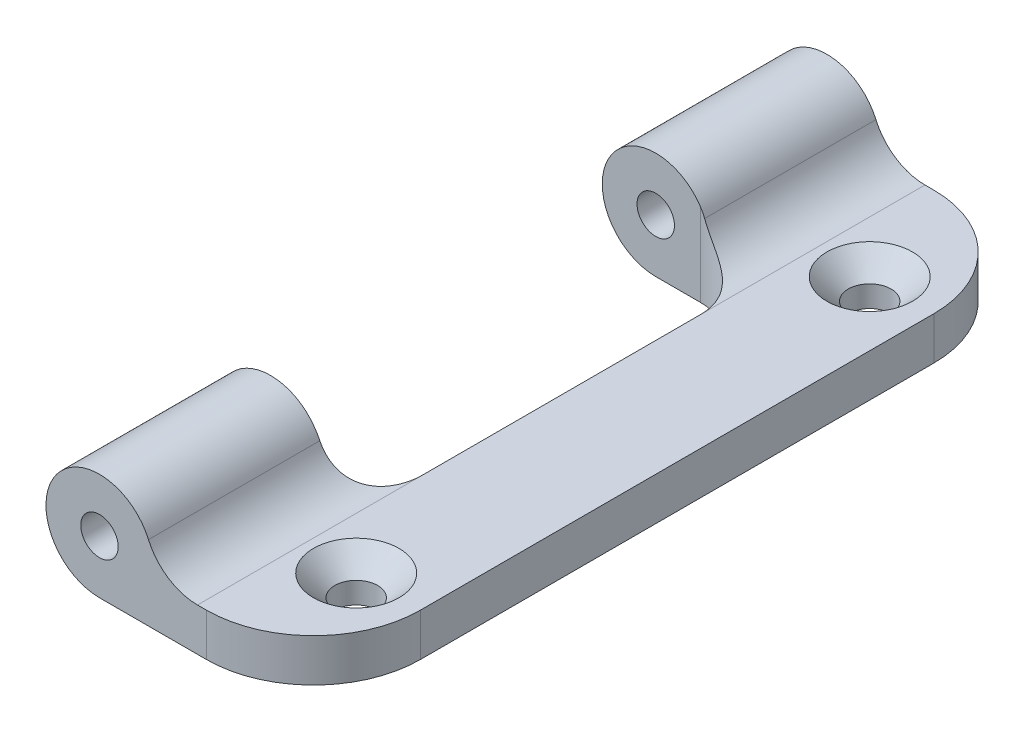
SolidWorks part; units mm, degrees
ref_plane "Plan de face" through (0, 0, 0) normal (0, 0, 1) x (1, 0, 0)
ref_plane "Plan de dessus" through (0, 0, 0) normal (0, 1, 0) x (1, 0, 0)
ref_plane "Plan de droite" through (0, 0, 0) normal (1, 0, 0) x (0, 0, -1)
sketch "Esquisse1" plane through (0, 0, 0) normal (0, 0, 1) x (1, 0, 0)
  line L0 (0, 0) -> (20, 0)
  line L1 (20, 0) -> (20, 4)
  line L2 (20, 4) -> (4.899, 4)
  circle A0 centre (0, 5) radius 1.75
  arc A1 (0, 0) -> (4.899, 4) centre (0, 5) cw
  dimension "D1" = 3.5
  dimension "D2" = 20
  dimension "D3" = 4
  dimension "D5" = 5
extrude "Boss.-Extru.1" add sketch "Esquisse1" along normal blind 68
fillet "Congé2" radius 5 2 edges at (4.899, 4, 34) (0, 0, 34)
sketch "Esquisse2" plane through (0, 4, 0) normal (0, 1, 0) x (1, 0, 0)
  line L0 (14, -68) -> (14, 0) construction
  line L3 (20, -34) -> (-12.3299, -34) construction
  line L4 (20, -68) -> (20, 0) construction
  line L5 (20, -68) -> (9.1652, -68) construction
  circle A0 centre (14, -10) radius 2
  circle A1 centre (14, -58) radius 2
  dimension "D1" = 4
  dimension "D2" = 48
  dimension "D3" = 6
extrude "Enlèv. mat.-Extru.1" cut sketch "Esquisse2" against normal through all both and the other way through all
chamfer "Chanfrein1" distance 2 angle 45 2 edges at (16, 4, 10) (16, 4, 58)
fillet "Congé3" radius 10 2 edges at (20, 2, 0) (20, 2, 68)
sketch "Esquisse3" plane through (0, 4, 0) normal (0, 1, 0) x (1, 0, 0)
  line L0 (20, -34) -> (-5, -34) construction
  line L1 (20, -58) -> (20, -10) construction
  line L2 (-5, 0) -> (-5, -68) construction
  line L3 (-5, -52) -> (-5, -16)
  line L4 (-5, -16) -> (9.1652, -16)
  line L5 (9.1652, 0) -> (9.1652, -68) construction
  line L6 (9.1652, -16) -> (9.1652, -52)
  line L7 (-5, -52) -> (9.1652, -52)
  point P12 (9.1652, -34)
  dimension "D1" = 36
extrude "Enlèv. mat.-Extru.3" cut sketch "Esquisse3" along normal through all both and the other way through all
fillet "Congé4" radius 5 2 edges at (9.1652, 2, 16) (9.1652, 2, 52)
